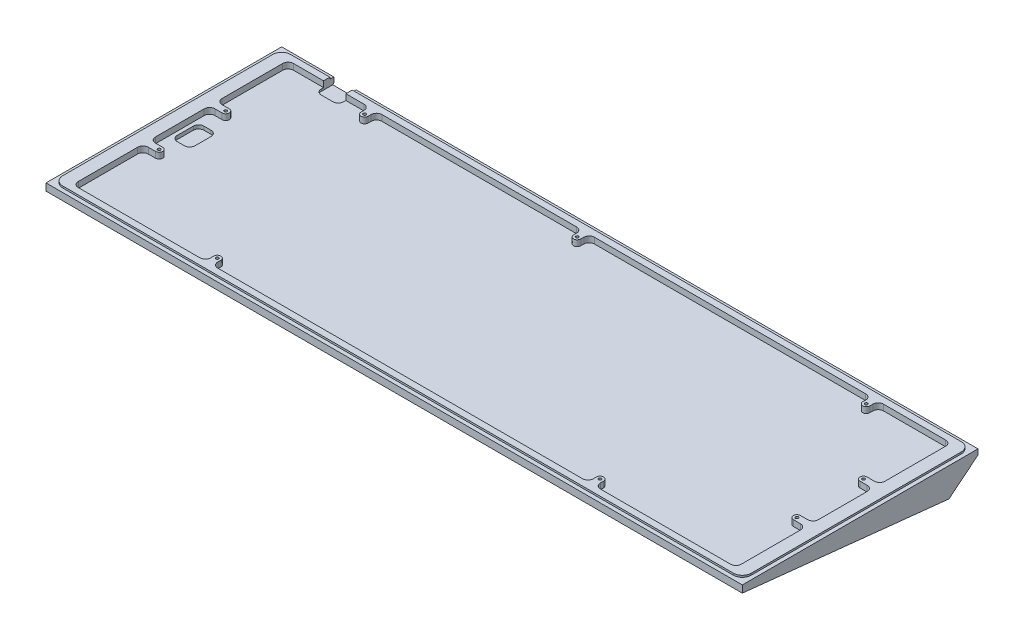
SolidWorks part; units mm, degrees
ref_plane "Front Plane" through (0, 0, 0) normal (0, 0, 1) x (1, 0, 0)
ref_plane "Top Plane" through (0, 0, 0) normal (0, 1, 0) x (1, 0, 0)
ref_plane "Right Plane" through (0, 0, 0) normal (1, 0, 0) x (0, 0, -1)
sketch "Sketch1" plane through (0, 0, 0) normal (0, 1, 0) x (1, 0, 0)
  line L1 (0, 0) -> (390, 0)
  line L2 (0, 0) -> (0, 132)
  line L3 (0, 132) -> (390, 132)
  line L4 (390, 0) -> (390, 132)
  dimension "D1" = 132
  dimension "D2" = 390
extrude "Boss-Extrude1" add sketch "Sketch1" along normal blind 40
sketch "Sketch2" plane through (0, 0, 0) normal (-1, 0, 0) x (0, 0, 1)
  line L0 (0, 36) -> (-115.7425, 23.835)
  line L1 (0, 40) -> (0, 0) construction
  line L2 (-115.7425, 23.835) -> (-132, 37)
  line L3 (-132, 40) -> (-132, 0) construction
  line L4 (-132, 40) -> (0, 40) construction
  dimension "D1" = 6
  dimension "D2" = 135
  dimension "D3" = 3
  dimension "D4" = 4
extrude "Cut-Extrude1" cut sketch "Sketch2" against normal through all and the other way through all
sketch "Sketch3" plane through (0, 40, 0) normal (0, 1, 0) x (1, 0, 0)
  line L0 (390, 132) -> (0, 132) construction
  line L1 (387.8, 2.2) -> (2.2, 2.2)
  line L2 (387.8, 2.2) -> (387.8, 129.8)
  line L3 (387.8, 129.8) -> (2.2, 129.8)
  line L4 (2.2, 2.2) -> (2.2, 129.8)
  line L5 (390, 0) -> (390, 132) construction
  line L6 (0, 0) -> (390, 0) construction
  point P4 (195, 129.8)
  point P7 (195, 132)
  point P8 (387.8, 66)
  point P11 (390, 66)
  dimension "D1" = 2.2
  dimension "D2" = 2.2
extrude "Boss-Extrude2" add sketch "Sketch3" along normal blind 1
sketch "Sketch4" plane through (0, 35.6067, -3.7424) normal (0, -0.9945, 0.1045) x (1, 0, 0)
  line L0 (197.9, -58.237) -> (195.9, -58.237) construction
  line L1 (197.9, -66.237) -> (195.9, -66.237)
  line L2 (197.9, -66.237) -> (197.9, -50.237)
  line L3 (197.9, -50.237) -> (195.9, -50.237)
  line L4 (195.9, -66.237) -> (195.9, -50.237)
  line L5 (202.4, -58.737) -> (200.4, -58.737)
  line L6 (202.4, -58.737) -> (202.4, -46.237)
  line L7 (202.4, -46.237) -> (200.4, -46.237)
  line L8 (200.4, -58.737) -> (200.4, -46.237)
  line L9 (193.1, -58.737) -> (191.1, -58.737)
  line L10 (193.1, -58.737) -> (193.1, -50.737)
  line L11 (193.1, -50.737) -> (191.1, -50.737)
  line L12 (191.1, -58.737) -> (191.1, -50.737)
  line L13 (189.6, -58.737) -> (187.6, -58.737)
  line L14 (189.6, -58.737) -> (189.6, -50.737)
  line L15 (189.6, -50.737) -> (187.6, -50.737)
  line L16 (187.6, -58.737) -> (187.6, -50.737)
  line L17 (186.1, -58.737) -> (184.1, -58.737)
  line L18 (186.1, -58.737) -> (186.1, -50.737)
  line L19 (186.1, -50.737) -> (184.1, -50.737)
  line L20 (184.1, -58.737) -> (184.1, -50.737)
  line L21 (202.4, -58.737) -> (187.6, -58.737) construction
  line L22 (193.9, -62.237) -> (197.9, -62.237)
  line L23 (193.9, -60.237) -> (197.9, -60.237)
  line L24 (205.9, -50.737) -> (203.9, -50.737)
  line L25 (205.9, -50.737) -> (205.9, -46.237)
  line L26 (205.9, -46.237) -> (203.9, -46.237)
  line L27 (203.9, -50.737) -> (203.9, -46.237)
  line L28 (205.9, -50.737) -> (184.1, -50.737) construction
  line L29 (0, -112.6171) -> (390, -112.6171) construction
  circle A0 centre (201.4, -61.237) radius 1
  circle A1 centre (193.9, -61.237) radius 1
  circle A2 centre (196.9, -65.237) radius 1
  circle A3 centre (196.9, -51.237) radius 1
  circle A4 centre (201.4, -57.737) radius 1
  circle A5 centre (201.4, -47.237) radius 1
  circle A6 centre (204.9, -49.737) radius 1
  circle A7 centre (204.9, -47.237) radius 1
  circle A8 centre (192.1, -57.737) radius 1
  circle A9 centre (192.1, -51.737) radius 1
  circle A10 centre (188.6, -57.737) radius 1
  circle A11 centre (188.6, -51.737) radius 1
  circle A12 centre (185.1, -57.737) radius 1
  circle A13 centre (185.1, -51.737) radius 1
  point P29 (201.4, -58.737)
  point P38 (196.9, -66.237)
  point P63 (195, -112.6171)
  point P64 (195, -50.737)
  dimension "D10" = 2
  dimension "D12" = 2
  dimension "D1" = 16
  dimension "D2" = 2
  dimension "D3" = 2.5
  dimension "D4" = 2.8
  dimension "D5" = 1.5
  dimension "D6" = 1.5
  dimension "D7" = 8
  dimension "D8" = 0.5
  dimension "D9" = 2.5
  dimension "D11" = 12.5
  dimension "D13" = 0
  dimension "D14" = 1.5
  dimension "D15" = 4.5
  dimension "D16" = 2
  dimension "D17" = 3
  dimension "D18" = 11
  dimension "D19" = 66.3801
extrude "Cut-Extrude2" cut sketch "Sketch4" against normal blind 1 contours A5 L8 A4 L6 | A6 | A7 L27 A6 L25 | A7 | A5 | A4 | A0 | A2 | A2 L2 L22 L4 | L23 L4 L22 L2 | A1 | A1 L22 L4 L23 | A3 L4 L23 L2 | A3 | A9 | A9 L12 A8 L10 | A8 | A11 L16 A10 L14 | A10 | A11 | A13 | A13 L20 A12 L18 | A12 region at (196.9, 28.7875, -68.622) region at (196.9, 28.9842, -66.7509) region at (196.9, 29.2056, -64.6439) region at (195.2722, 29.2056, -64.6439) region at (196.9, 29.7398, -59.5616) region at (193.9, 29.2056, -64.6439) region at (196.9, 30.2509, -54.6987) region at (201.4, 29.5715, -61.1631) region at (201.4, 30.1203, -55.9419) region at (201.4, 30.669, -50.7206) region at (192.1, 29.5715, -61.1631) region at (192.1, 29.8851, -58.1795) region at (192.1, 30.1987, -55.196) region at (188.6, 29.5715, -61.1631) region at (188.6, 29.8851, -58.1795) region at (188.6, 30.1987, -55.196) region at (185.1, 29.5715, -61.1631) region at (185.1, 29.8851, -58.1795) region at (185.1, 30.1987, -55.196) region at (204.9, 30.4077, -53.2069) region at (204.9, 30.5384, -51.9638) region at (204.9, 30.669, -50.7206) region at (201.4, 29.2056, -64.6439)
sketch "Sketch5" plane through (0, 41, 0) normal (0, 1, 0) x (1, 0, 0)
  line L0 (0, 132) -> (390, 132) construction
  line L1 (9.35, 126.2375) -> (380.65, 126.2375)
  line L2 (9.35, 126.2375) -> (9.35, 5.7625)
  line L3 (9.35, 5.7625) -> (380.65, 5.7625)
  line L4 (380.65, 126.2375) -> (380.65, 5.7625)
  line L6 (2.2, 129.8) -> (2.2, 2.2) construction
  line L9 (171.1875, 124.7375) -> (61.65, 124.7375) construction
  line L10 (10.85, 123.2389) -> (10.85, 89.0188) construction
  point P6 (195, 132)
  point P7 (195, 126.2375)
  point P12 (2.2, 66)
  point P13 (9.35, 66)
  dimension "D1" = 1.5
  dimension "D2" = 1.5
extrude "Cut-Extrude3" cut sketch "Sketch5" against normal blind 3.3
sketch "Sketch6" plane through (0, 37.7, 0) normal (0, 1, 0) x (1, 0, 0)
  line L0 (16.4062, 48.95) -> (16.4062, 44.95)
  line L1 (16.4062, 48.95) -> (9.35, 48.95)
  line L2 (16.4062, 44.95) -> (9.35, 44.95)
  line L3 (9.35, 48.95) -> (9.35, 44.95)
  line L4 (16.4062, 86.2562) -> (16.4062, 82.2563)
  line L5 (16.4062, 86.2562) -> (9.35, 86.2562)
  line L6 (16.4062, 82.2563) -> (9.35, 82.2563)
  line L7 (9.35, 86.2562) -> (9.35, 82.2563)
  line L8 (9.35, 126.2375) -> (9.35, 5.7625) construction
  line L9 (54.8875, 121.5625) -> (58.8875, 121.5625)
  line L10 (54.8875, 121.5625) -> (54.8875, 126.2375)
  line L11 (58.8875, 121.5625) -> (58.8875, 126.2375)
  line L12 (54.8875, 126.2375) -> (58.8875, 126.2375)
  line L13 (380.65, 126.2375) -> (9.35, 126.2375) construction
  line L14 (173.95, 121.5625) -> (177.95, 121.5625)
  line L15 (173.95, 121.5625) -> (173.95, 126.2375)
  line L16 (177.95, 121.5625) -> (177.95, 126.2375)
  line L17 (173.95, 126.2375) -> (177.95, 126.2375)
  line L18 (335.875, 121.5625) -> (339.875, 121.5625)
  line L19 (335.875, 121.5625) -> (335.875, 126.2375)
  line L20 (339.875, 121.5625) -> (339.875, 126.2375)
  line L21 (335.875, 126.2375) -> (339.875, 126.2375)
  line L22 (373.5937, 86.288) -> (373.5937, 82.288)
  line L23 (373.5937, 86.288) -> (380.65, 86.288)
  line L24 (373.5937, 82.288) -> (380.65, 82.288)
  line L25 (380.65, 86.288) -> (380.65, 82.288)
  line L26 (373.5937, 48.95) -> (373.5937, 44.95)
  line L27 (373.5937, 48.95) -> (380.65, 48.95)
  line L28 (373.5937, 44.95) -> (380.65, 44.95)
  line L29 (380.65, 48.95) -> (380.65, 44.95)
  line L30 (297.775, 10.475) -> (301.775, 10.475)
  line L31 (297.775, 10.475) -> (297.775, 5.7625)
  line L32 (301.775, 10.475) -> (301.775, 5.7625)
  line L33 (297.775, 5.7625) -> (301.775, 5.7625)
  line L34 (83.4625, 10.475) -> (87.4625, 10.475)
  line L35 (83.4625, 10.475) -> (83.4625, 5.7625)
  line L36 (87.4625, 10.475) -> (87.4625, 5.7625)
  line L37 (83.4625, 5.7625) -> (87.4625, 5.7625)
  line L38 (9.35, 5.7625) -> (380.65, 5.7625) construction
  line L39 (380.65, 5.7625) -> (380.65, 126.2375) construction
  circle A0 centre (16.4062, 84.2563) radius 2
  circle A1 centre (56.8875, 121.5625) radius 2
  circle A2 centre (175.95, 121.5625) radius 2
  circle A3 centre (337.875, 121.5625) radius 2
  circle A4 centre (373.5937, 84.288) radius 2
  circle A5 centre (373.5937, 46.95) radius 2
  circle A6 centre (299.775, 10.475) radius 2
  circle A7 centre (85.4625, 10.475) radius 2
  circle A8 centre (16.4062, 46.95) radius 2
  arc A9 (16.4062, 82.2562) -> (16.4062, 86.2562) centre (16.4062, 84.2562) ccw construction
  arc A10 (16.4062, 44.95) -> (16.4062, 48.95) centre (16.4062, 46.95) ccw construction
  arc A11 (87.4625, 10.475) -> (83.4625, 10.475) centre (85.4625, 10.475) ccw construction
  arc A12 (301.775, 10.475) -> (297.775, 10.475) centre (299.775, 10.475) ccw construction
  arc A13 (373.5937, 48.95) -> (373.5937, 44.95) centre (373.5937, 46.95) ccw construction
  arc A14 (373.5937, 86.288) -> (373.5937, 82.288) centre (373.5937, 84.288) ccw construction
  arc A15 (335.875, 121.5625) -> (339.875, 121.5625) centre (337.875, 121.5625) ccw construction
  arc A16 (173.95, 121.5625) -> (177.95, 121.5625) centre (175.95, 121.5625) ccw construction
  arc A17 (54.8875, 121.5625) -> (58.8875, 121.5625) centre (56.8875, 121.5625) ccw construction
  line M2 (9.35, 126.2375) -> (9.35, 5.7625)
  line M3 (9.35, 5.7625) -> (380.65, 5.7625)
  line M4 (380.65, 5.7625) -> (380.65, 126.2375)
  line M5 (380.65, 126.2375) -> (9.35, 126.2375)
extrude "Boss-Extrude3" add sketch "Sketch6" along normal up to surface (3.3 mm away) contours A0 L5 L6 M2 | L4 A0 | L4 A0 | A8 L1 L3 L2 | L0 A8 | L0 A8 | L9 A1 | L9 A1 | A1 L11 L10 M5 | L14 A2 | L14 A2 | A2 L16 L15 M5 | L18 A3 | L18 A3 | A3 L20 L19 M5 | L22 A4 | A4 L24 L23 M4 | L22 A4 | L26 A5 | L26 A5 | A5 L28 L27 M4 | A6 L31 L32 M3 | L30 A6 | L30 A6 | A7 L35 L36 M3 | L34 A7 | L34 A7 region at (17.2551, 37.7, -46.95) region at (12.1109, 37.7, -46.95) region at (15.5574, 37.7, -46.95) region at (12.1109, 37.7, -84.2563) region at (15.5574, 37.7, -84.2563) region at (17.2551, 37.7, -84.2563) region at (85.4625, 37.7, -7.3651) region at (85.4625, 37.7, -11.3238) region at (85.4625, 37.7, -9.6262) region at (56.8875, 37.7, -124.6533) region at (299.775, 37.7, -7.3651) region at (56.8875, 37.7, -122.4113) region at (56.8875, 37.7, -120.7137) region at (299.775, 37.7, -11.3238) region at (299.775, 37.7, -9.6262) region at (175.95, 37.7, -124.6533) region at (175.95, 37.7, -122.4113) region at (175.95, 37.7, -120.7137) region at (377.8891, 37.7, -46.95) region at (337.875, 37.7, -124.6533) region at (372.7449, 37.7, -46.95) region at (374.4426, 37.7, -46.95) region at (337.875, 37.7, -122.4113) region at (337.875, 37.7, -120.7137) region at (377.8891, 37.7, -84.288) region at (372.7449, 37.7, -84.288) region at (374.4426, 37.7, -84.288) up to face at (195, 41, -66)
sketch "Sketch7" plane through (0, 0, -132) normal (0, 0, -1) x (-1, 0, 0)
  line L1 (-41.7062, 41) -> (-29.2062, 41)
  line L2 (-41.7062, 41) -> (-41.7062, 36.5)
  line L3 (-41.7062, 36.5) -> (-29.2062, 36.5)
  line L4 (-29.2062, 41) -> (-29.2062, 36.5)
  line L5 (-41.7062, 42.8) -> (-41.7062, 40) construction
  line L6 (-29.2062, 40) -> (-29.2062, 42.8) construction
  line L7 (-387.8, 41) -> (-2.2, 41) construction
  dimension "D1" = 4.5
extrude "Cut-Extrude4" cut sketch "Sketch7" against normal blind 10
sketch "Sketch8" plane through (0, 41, 0) normal (0, 1, 0) x (1, 0, 0)
  point P0 (16.4062, 84.2562)
  point P1 (16.4062, 46.95)
  point P3 (85.4625, 10.475)
  point P5 (299.775, 10.475)
  point P7 (373.5937, 46.95)
  point P9 (373.5937, 84.288)
  point P11 (337.875, 121.5625)
  point P13 (175.95, 121.5625)
  point P15 (56.8875, 121.5625)
hole_wizard "M2x0.4 Tapped Hole1" positions "3DSketch1" profile "Sketch9" tap size "M2x0.4" standard "ANSI Metric"
sketch3d "3DSketch1"
  point P0 (16.4062, 41, -84.2562)
  point P3 (16.4062, 41, -46.95)
  point P6 (85.4625, 41, -10.475)
  point P9 (56.8875, 41, -121.5625)
  point P12 (175.95, 41, -121.5625)
  point P15 (299.775, 41, -10.475)
  point P18 (373.5937, 41, -46.95)
  point P21 (373.5937, 41, -84.288)
  point P24 (337.875, 41, -121.5625)
sketch "Sketch9" plane through (16.4062, 41, -84.2562) normal (1, 0, 0) x (0, 0, 1)
  line L0 (0, 0) -> (0, 4.4807)
  line L1 (0, 4.4807) -> (0.8, 4)
  line L2 (0.8, 4) -> (0.8, 0)
  line L5 (0.8, 0) -> (0, 0)
  line L10 (0, 4.4807) -> (-0.8, 4) construction
  line L11 (0, -6.35) -> (0, 107.95) construction
  dimension "Tap Drill Dia." = 1.6
  dimension "Tap Drill Depth" = 4
  dimension "Drill Angle" = 118
cosmetic thread "Hole Thread1" parameters "D1"=4, "D2"=2
cosmetic thread "Hole Thread2" parameters "D1"=4, "D2"=2
cosmetic thread "Hole Thread3" parameters "D1"=4, "D2"=2
cosmetic thread "Hole Thread4" parameters "D1"=4, "D2"=2
cosmetic thread "Hole Thread5" parameters "D1"=4, "D2"=2
cosmetic thread "Hole Thread6" parameters "D1"=4, "D2"=2
cosmetic thread "Hole Thread7" parameters "D1"=4, "D2"=2
cosmetic thread "Hole Thread8" parameters "D1"=4, "D2"=2
cosmetic thread "Hole Thread9" parameters "D1"=4, "D2"=2
sketch "Sketch10" plane through (0, 37.7, 0) normal (0, 1, 0) x (1, 0, 0)
  line L0 (13.1562, 72.441) -> (19.6562, 72.441) construction
  line L1 (11.4062, 74.0715) -> (21.4062, 74.0715)
  line L2 (11.4062, 74.0715) -> (11.4062, 59.0715)
  line L3 (11.4062, 59.0715) -> (21.4062, 59.0715)
  line L4 (21.4062, 74.0715) -> (21.4062, 59.0715)
  line L5 (13.1562, 60.702) -> (19.6562, 60.702) construction
  line L6 (16.4062, 72.441) -> (16.4062, 60.702) construction
  point P14 (11.4062, 66.5715)
  point P15 (16.4062, 66.5715)
  point P16 (16.4062, 74.0715)
  dimension "D1" = 15
  dimension "D2" = 10
extrude "Cut-Extrude5" cut sketch "Sketch10" against normal blind 2
fillet "Fillet1" radius 3 28 edges at (41.7062, 37.1, -122) (29.2062, 37.1, -122) (380.65, 39.35, -5.7625) (380.65, 39.35, -126.2375) (9.35, 39.35, -126.2375) (9.35, 39.35, -5.7625) (83.4625, 39.35, -5.7625) (87.4625, 39.35, -5.7625) (301.775, 39.35, -5.7625) (297.775, 39.35, -5.7625) (380.65, 39.35, -86.288) (380.65, 39.35, -48.95) (380.65, 39.35, -44.95) (380.65, 39.35, -82.288) (335.875, 39.35, -126.2375) (339.875, 39.35, -126.2375) (177.95, 39.35, -126.2375) (173.95, 39.35, -126.2375) (54.8875, 39.35, -126.2375) (58.8875, 39.35, -126.2375) (9.35, 39.35, -82.2563) (9.35, 39.35, -86.2562) (9.35, 39.35, -48.95) (9.35, 39.35, -44.95) (21.4062, 36.7, -59.0715) (11.4062, 36.7, -59.0715) (11.4062, 36.7, -74.0715) (21.4062, 36.7, -74.0715)
fillet "Fillet2" radius 5 4 edges at (387.8, 40.5, -129.8) (387.8, 40.5, -2.2) (2.2, 40.5, -2.2) (2.2, 40.5, -129.8)
